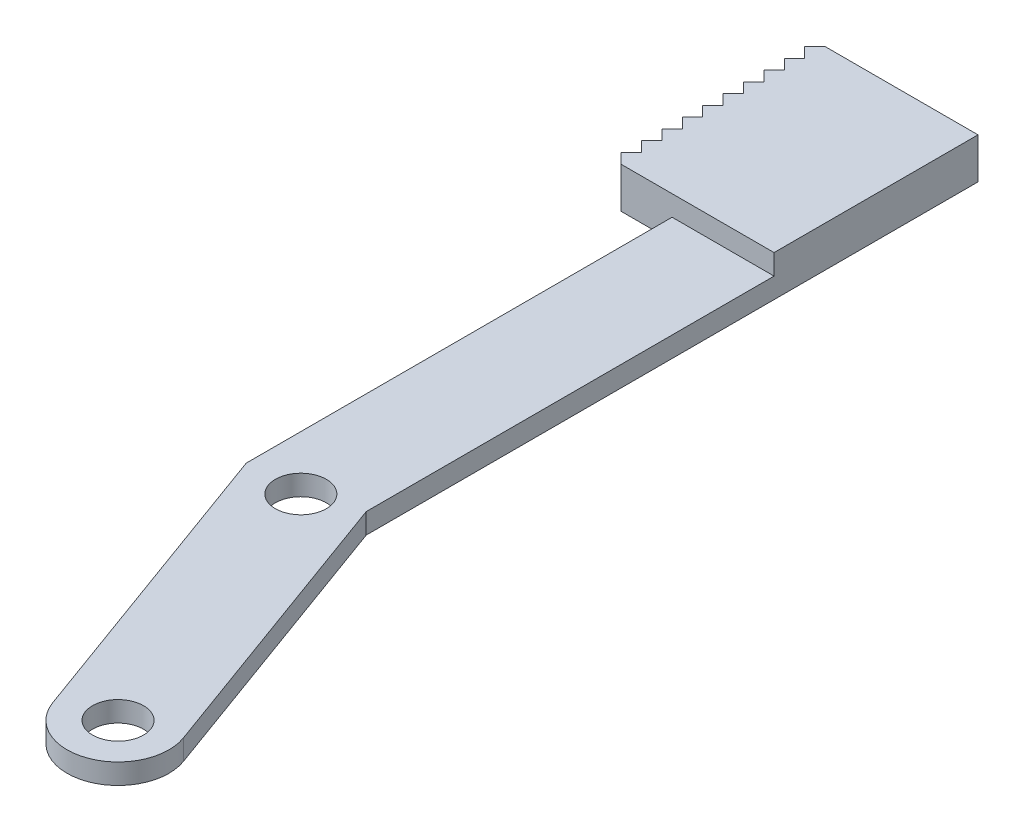
SolidWorks part; units mm, degrees
ref_plane "Front Plane" through (0, 0, 0) normal (0, 0, 1) x (1, 0, 0)
ref_plane "Top Plane" through (0, 0, 0) normal (0, 1, 0) x (1, 0, 0)
ref_plane "Right Plane" through (0, 0, 0) normal (1, 0, 0) x (0, 0, -1)
sketch "Sketch1" plane through (0, 0, 0) normal (0, 1, 0) x (1, 0, 0)
  line L0 (-6.35, -14.9394) -> (-6.35, 38.1)
  line L1 (6.35, -12.7) -> (6.35, 63.5)
  line L2 (6.35, 63.5) -> (-12.7, 63.5)
  line L3 (-12.7, 63.5) -> (-12.7, 38.1)
  line L4 (-12.7, 38.1) -> (-6.35, 38.1)
  line L5 (6.35, -12.7) -> (19.381, -48.5023)
  line L6 (-6.35, -14.9394) -> (7.4469, -52.8459)
  line L7 (6.35, -12.7) -> (-5.5841, -17.0437) construction
  arc A0 (7.4469, -52.8459) -> (19.381, -48.5023) centre (13.4139, -50.6741) ccw
  circle A1 centre (13.4139, -50.6741) radius 3.175
  circle A2 centre (0.383, -14.8718) radius 3.175
  dimension "D1" = 6.35
  dimension "D2" = 6.35
  dimension "D6" = 6.35
  dimension "D3" = 160
  dimension "D4" = 12.7
  dimension "D5" = 6.35
  dimension "D8" = 38.1
  dimension "D10" = 19.05
  dimension "D11" = 76.2
  dimension "D12" = 25.4
  dimension "D13" = 12.7
extrude "Boss-Extrude1" add sketch "Sketch1" along normal blind 5.08
sketch "Sketch2" plane through (0, 5.08, 0) normal (0, 1, 0) x (1, 0, 0)
  line L1 (-6.35, -14.9394) -> (9.6187, -58.813)
  line L2 (6.35, -12.7) -> (21.5528, -54.4693)
  line L3 (21.5528, -54.4693) -> (9.6187, -58.813)
  line L4 (-6.35, -14.9394) -> (7.4469, -52.8459) construction
  line L5 (19.381, -48.5023) -> (6.35, -12.7) construction
  line L6 (-6.35, 38.1) -> (6.35, 38.1)
  line L7 (6.35, -12.7) -> (6.35, 63.5) construction
  line L8 (6.35, 38.1) -> (6.35, -12.7)
  line L9 (-6.35, -14.9394) -> (-6.35, 38.1)
  arc A0 (7.4469, -52.8459) -> (19.381, -48.5023) centre (13.4139, -50.6741) ccw construction
extrude "Right Cut" cut sketch "Sketch2" against normal blind 2.54
sketch "Sketch3" plane through (0, 5.08, 0) normal (0, 1, 0) x (1, 0, 0)
  line L0 (-12.7, 63.5) -> (-13.97, 62.23)
  line L1 (-13.97, 62.23) -> (-12.7, 60.96)
  line L2 (-12.7, 63.5) -> (-12.7, 38.1) construction
  line L12 (-12.7, 63.5) -> (6.35, 63.5)
  line L13 (6.35, 63.5) -> (6.35, 38.1)
  line L14 (6.35, 38.1) -> (6.35, 63.5) construction
  line L16 (-13.97, 59.69) -> (-12.7, 58.42)
  line L17 (-12.7, 60.96) -> (-13.97, 59.69)
  line L18 (-13.97, 57.15) -> (-12.7, 55.88)
  line L19 (-12.7, 58.42) -> (-13.97, 57.15)
  line L20 (-13.97, 54.61) -> (-12.7, 53.34)
  line L21 (-12.7, 55.88) -> (-13.97, 54.61)
  line L22 (-13.97, 52.07) -> (-12.7, 50.8)
  line L23 (-12.7, 53.34) -> (-13.97, 52.07)
  line L24 (-13.97, 49.53) -> (-12.7, 48.26)
  line L25 (-12.7, 50.8) -> (-13.97, 49.53)
  line L26 (-13.97, 46.99) -> (-12.7, 45.72)
  line L27 (-12.7, 48.26) -> (-13.97, 46.99)
  line L28 (-13.97, 44.45) -> (-12.7, 43.18)
  line L29 (-12.7, 45.72) -> (-13.97, 44.45)
  line L30 (-13.97, 41.91) -> (-12.7, 40.64)
  line L31 (-12.7, 43.18) -> (-13.97, 41.91)
  line L32 (-13.97, 39.37) -> (-12.7, 38.1)
  line L33 (-12.7, 40.64) -> (-13.97, 39.37)
  line L34 (-12.7, 38.1) -> (6.35, 38.1)
  dimension "D1" = 2.54
  dimension "D2" = 135
  dimension "D3" = 10
extrude "Boss-Extrude2" add sketch "Sketch3" against normal up to surface (5.08 mm away) contours L13 L34 L32 L33 L30 L31 L28 L29 L26 L27 L24 L25 L22 L23 L20 L21 L18 L19 L16 L17 L1 L0 L12 up to face at (0.45, 0, -8.5307)
sketch "Sketch4" plane through (0, 0, 0) normal (0, -1, 0) x (1, 0, 0)
  line L0 (-6.35, -38.1) -> (-6.35, 14.9394)
  line L1 (-6.35, 14.9394) -> (7.4469, 52.8459) construction
  line L2 (-6.35, -38.1) -> (-6.35, 14.9394) construction
  line L3 (-6.35, 14.9394) -> (9.6187, 58.813)
  line L4 (9.6187, 58.813) -> (21.5528, 54.4693)
  line L5 (-6.35, -38.1) -> (6.35, -38.1)
  line L7 (6.35, -38.1) -> (6.35, 12.7)
  line L8 (6.35, 12.7) -> (21.5528, 54.4693)
  line L9 (19.381, 48.5023) -> (6.35, 12.7) construction
  arc A0 (19.381, 48.5023) -> (7.4469, 52.8459) centre (13.4139, 50.6741) ccw construction
extrude "Left Cut" [suppressed] cut sketch "Sketch4" against normal blind 2.54
